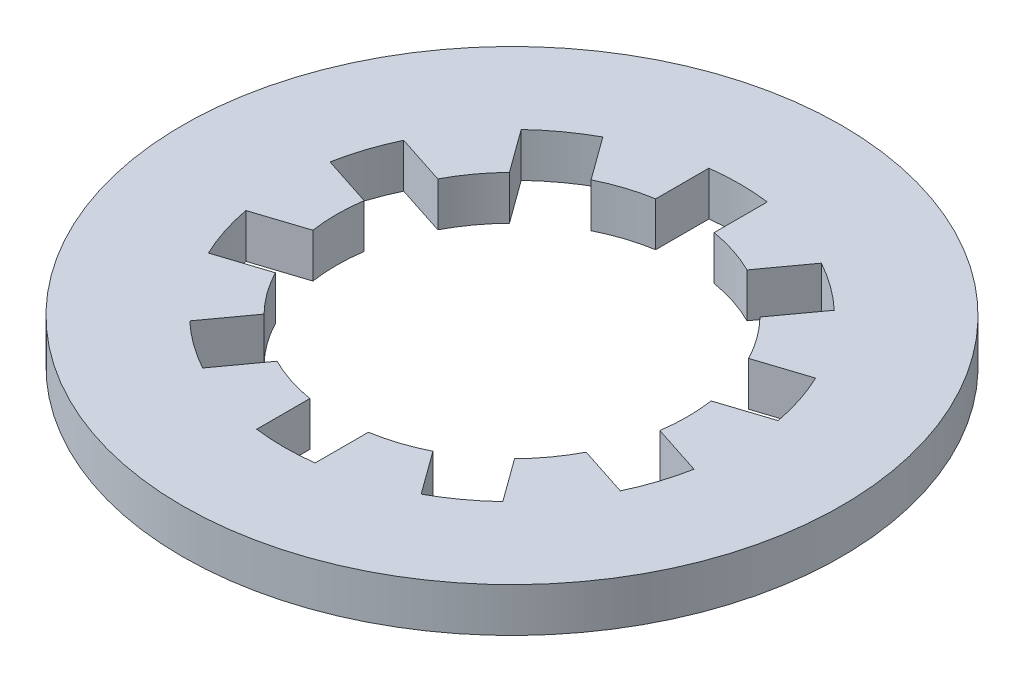
SolidWorks part; units mm, degrees
ref_plane "Front Plane" through (0, 0, 0) normal (0, 0, 1) x (1, 0, 0)
ref_plane "Top Plane" through (0, 0, 0) normal (0, 1, 0) x (1, 0, 0)
ref_plane "Right Plane" through (0, 0, 0) normal (1, 0, 0) x (0, 0, -1)
sketch "Sketch1" plane through (0, 0, 0) normal (0, 1, 0) x (1, 0, 0)
  line L0 (0, 0) -> (0, 7.5854) construction
  circle A0 centre (0, 0) radius 9.4996
  circle A1 centre (0, 0) radius 5.0546
  dimension "B" = 18.9992
  dimension "A" = 10.1092
extrude "Extrude1" add sketch "Sketch1" along normal blind 1.27
sketch "Sketch2" plane through (0, 1.27, 0) normal (0, 1, 0) x (-1, 0, 0)
  line L0 (0, 0) -> (0, 0.5002) construction
  line L1 (0, 0) -> (0, 9.2629) construction
  line L4 (-0.8424, 6.5168) -> (-0.8424, 4.9839)
  line L6 (0.8424, 6.5168) -> (0.8424, 4.9839)
  circle A0 centre (0, 0) radius 5.0546 construction
  arc A1 (0.8424, 4.9839) -> (-0.8424, 4.9839) centre (0, 0) ccw
  arc A2 (0.8424, 6.5168) -> (-0.8424, 6.5168) centre (0, 0) ccw
  dimension "D1" = 13.142
extrude "Cut-Extrude1" cut sketch "Sketch2" against normal through all
ref_axis "Axis1" through (0, 8.8667, 0) along (0, -1, 0)
pattern_circular "CirPattern1" count 10 over 360 about axis through (0, 8.8667, 0) along (0, -1, 0) of "Cut-Extrude1"
pattern_circular "CirPattern2" [suppressed] count 9 over 360 about axis through (0, 8.8667, 0) along (0, -1, 0) of bodies 102
equation "\"D1@Sketch2\" = \"A@Sketch1\" * 1.3"
equation "\"D2@Sketch2\" = \"A@Sketch1\" / 6"
